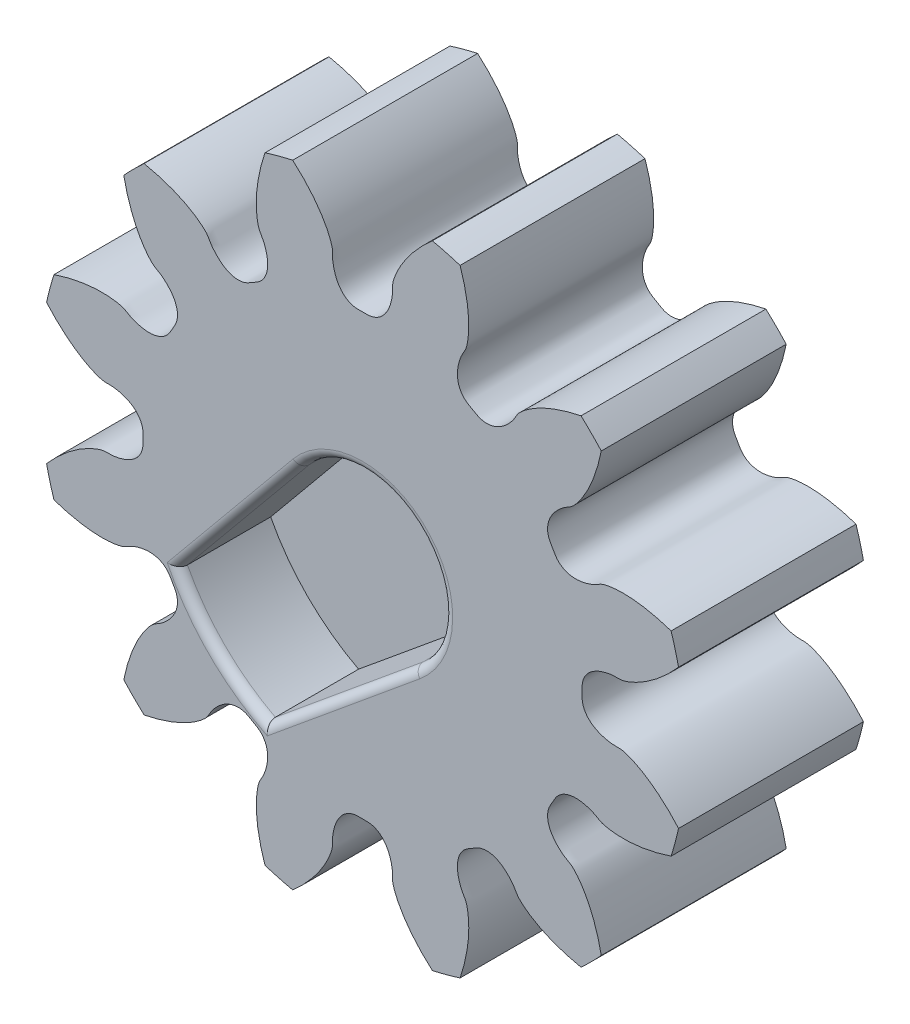
SolidWorks part; units mm, degrees
material "聚脂树脂"
ref_plane "前视基准面" through (0, 0, 0) normal (0, 0, 1) x (1, 0, 0)
ref_plane "上视基准面" through (0, 0, 0) normal (0, 1, 0) x (1, 0, 0)
ref_plane "右视基准面" through (0, 0, 0) normal (1, 0, 0) x (0, 0, -1)
ref_axis "基准轴1" through (0, 0, 55) along (0, 0, -1)
sketch "旋转草图小直齿轮" plane through (0, 0, 0) normal (1, 0, 0) x (0, 0, -1)
  line L0 (0, 0) -> (1, 0) construction
  line L1 (-10, 0) -> (-10, 14)
  line L2 (-10, 14) -> (10, 14)
  line L3 (10, 14) -> (10, 0)
  line L4 (10, 0) -> (-10, 0)
revolve "小直齿轮" add sketch "旋转草图小直齿轮" angle 360 about L0
sketch "齿草图小直齿轮" plane through (0, 0, 0) normal (0, 0, 1) x (1, 0, 0)
  arc A0 (13.7517, 3.1147) -> (13.7517, -3.1147) centre (0, 0) cw
  spline S0 degree 3 poles (13.7517, -3.1147) (13.6214, -2.9614) (13.4232, -2.7441) (13.1503, -2.4777) (12.956, -2.3017) (12.7674, -2.1434) (12.5855, -2.002) (12.4113, -1.8767) (12.2458, -1.7669) (12.0899, -1.6717) (11.9444, -1.5901) (11.8101, -1.5212) (11.6876, -1.4642) (11.5778, -1.4179) (11.4812, -1.3813) (11.3684, -1.3438) (11.1393, -1.2767) (10.8938, -1.3096) (10.6796, -1.2754) (10.5857, -1.2584) (10.4947, -1.2376) (10.4063, -1.2135) (10.3206, -1.186) (10.2376, -1.1548) (10.1572, -1.1198) (10.0794, -1.0808) (10.0042, -1.0375) (9.9318, -0.9893) (9.8622, -0.9359) (9.7958, -0.8767) (9.733, -0.8111) (9.6748, -0.7384) (9.6221, -0.6582) (9.5764, -0.5702) (9.5395, -0.4748) (9.513, -0.3729) (9.5009, -0.2772) (9.496, -0.1524) (9.5029, 0) (9.496, 0.1524) (9.5009, 0.2772) (9.513, 0.3729) (9.5395, 0.4748) (9.5764, 0.5702) (9.6221, 0.6582) (9.6748, 0.7384) (9.733, 0.8111) (9.7958, 0.8767) (9.8622, 0.9359) (9.9318, 0.9893) (10.0042, 1.0375) (10.0794, 1.0808) (10.1572, 1.1198) (10.2376, 1.1548) (10.3206, 1.186) (10.4063, 1.2135) (10.4947, 1.2376) (10.5857, 1.2584) (10.6796, 1.2754) (10.8938, 1.3096) (11.1393, 1.2767) (11.3684, 1.3438) (11.4812, 1.3813) (11.5778, 1.4179) (11.6876, 1.4642) (11.8101, 1.5212) (11.9444, 1.5901) (12.0899, 1.6717) (12.2458, 1.7669) (12.4113, 1.8767) (12.5855, 2.002) (12.7674, 2.1434) (12.956, 2.3017) (13.1503, 2.4777) (13.4232, 2.7441) (13.6214, 2.9614) (13.7517, 3.1147) knots 0 0 0 0 0.053498 0.078135 0.101365 0.123186 0.1436 0.162606 0.180204 0.196394 0.211177 0.224551 0.236518 0.247077 0.256227 0.263971 0.278716 0.319236 0.327883 0.336333 0.344603 0.352711 0.360676 0.368523 0.376279 0.383975 0.391648 0.399337 0.407088 0.41495 0.422972 0.431203 0.439686 0.448451 0.457505 0.466826 0.476364 0.483109 0.5 0.516891 0.523636 0.533174 0.542495 0.551549 0.560314 0.568797 0.577028 0.58505 0.592912 0.600663 0.608352 0.616025 0.623721 0.631477 0.639324 0.647289 0.655397 0.663667 0.672117 0.680764 0.721284 0.736029 0.743773 0.752923 0.763482 0.775449 0.788823 0.803606 0.819796 0.837394 0.8564 0.876814 0.898635 0.921865 0.946502 1 1 1 1
extrude "齿拉伸切除小直齿轮" cut sketch "齿草图小直齿轮" against normal blind 10 and the other way blind 10
pattern_circular "齿形小直齿轮" count 12 every 30 about axis through (0, 0, 55) along (0, 0, -1) of "齿拉伸切除小直齿轮"
sketch "辅助草图小直齿轮" plane through (0, 0, 10) normal (0, 0, 1) x (1, 0, 0)
  circle A0 centre (0, 0) radius 12 construction
  circle A1 centre (0, 0) radius 11.2763 construction
  circle A2 centre (0, 0) radius 11.4613 construction
  circle A3 centre (0, 0) radius 14 construction
  circle A4 centre (0, 0) radius 9.5 construction
  dimension "PitchDiameter" = 24
  dimension "BaseDiameter" = 22.5526
  dimension "FormDiameter" = 22.9226
  dimension "MajorDiameter" = 28
  dimension "MinorDiameter" = 19
sketch "草图1" plane through (0, 0, 10) normal (0, 0, 1) x (1, 0, 0)
  line L0 (-8.3923, -11.454) -> (2.2263, -2.7007)
  line L3 (-11.454, -8.3923) -> (-2.7007, 2.2263)
  line L4 (-9.7758, -9.7758) -> (0, 0) construction
  line L5 (0, 0) -> (21.6782, 0) construction
  circle A0 centre (0, 0) radius 3.5
  circle A3 centre (-9.7758, -9.7758) radius 2.175
  circle A5 centre (0, 0) radius 9
  dimension "D1" = 7
  dimension "D3" = 16
  dimension "D2" = 4.35
  dimension "D5" = 18
  dimension "D4" = 135
extrude "切除-拉伸1" cut sketch "草图1" against normal blind 4 contours A0 | L3 A5 L0 A0 region at (-4.0417, -4.0417, 10) region at (0, 0, 10)
sketch "草图2" plane through (0, 0, -10) normal (0, 0, -1) x (-1, 0, 0)
  circle A0 centre (0, 0) radius 22.9837
extrude "切除-拉伸2" cut sketch "草图2" against normal offset from surface (12 mm away) 8 up to face at (-2.5499, -2.5499, 10)
sketch "草图3" plane through (0, 0, 10) normal (0, 0, 1) x (1, 0, 0)
  circle A0 centre (0, 0) radius 1
  dimension "D1" = 2
extrude "切除-拉伸3" cut sketch "草图3" against normal blind 8
fillet "圆角1" radius 0.4 4 edges at (-0.9727, -5.3377, 10) (2.4749, 2.4749, 10) (-6.364, -6.364, 10) (-5.3377, -0.9727, 10)
sketch "草图4" plane through (0, 0, 2) normal (0, 0, -1) x (-1, 0, 0)
  circle A0 centre (0, 0) radius 3.5
  dimension "D1" = 7
extrude "切除-拉伸4" cut sketch "草图4" against normal offset from surface (1 mm away) 3 up to face at (1, 0, 6)
